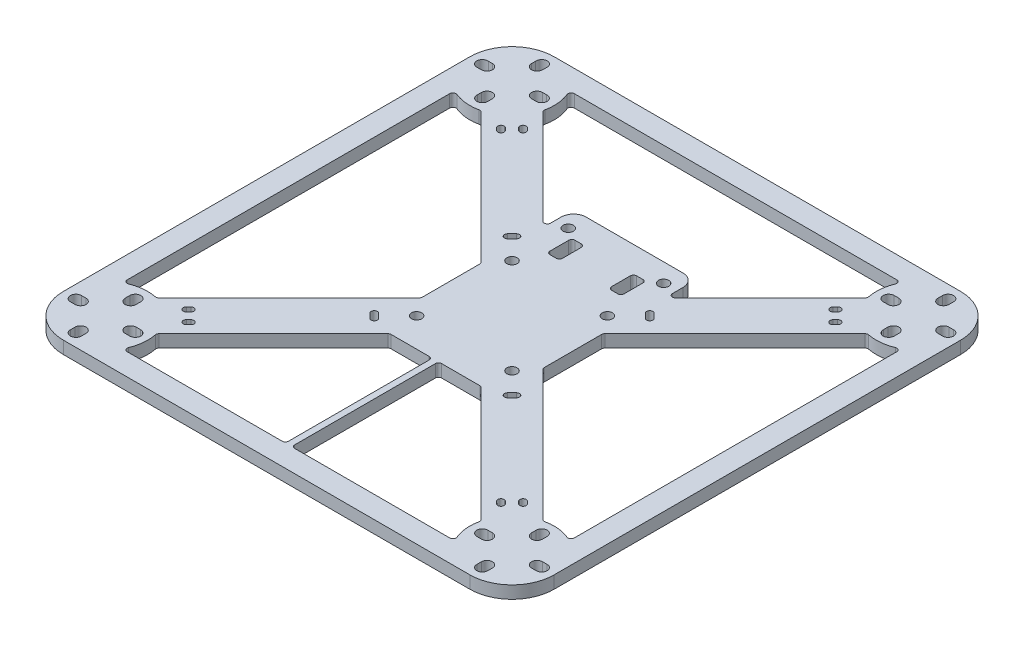
SolidWorks part; units mm, degrees
ref_plane "Front Plane" through (0, 0, 0) normal (0, 0, 1) x (1, 0, 0)
ref_plane "Top Plane" through (0, 0, 0) normal (0, 1, 0) x (1, 0, 0)
ref_plane "Right Plane" through (0, 0, 0) normal (1, 0, 0) x (0, 0, -1)
sketch "Sketch1" plane through (0, 0, 0) normal (0, 1, 0) x (1, 0, 0)
  line L0 (0, 78.5) -> (0, -78.5) construction
  line L1 (-78.5, 78.5) -> (78.5, 78.5)
  line L2 (-78.5, 78.5) -> (-78.5, -78.5)
  line L3 (-78.5, -78.5) -> (78.5, -78.5)
  line L4 (78.5, 78.5) -> (78.5, -78.5)
  line L5 (-78.5, 78.5) -> (78.5, -78.5) construction
  line L6 (-78.5, -78.5) -> (78.5, 78.5) construction
  line L7 (78.5, 0) -> (-78.5, 0) construction
  line L8 (-1, 65) -> (-1, 0) construction
  line L9 (-83.4497, 73.5503) -> (73.5503, -83.4497)
  line L10 (-73.5503, 83.4497) -> (83.4497, -73.5503)
  line L11 (-73.5503, -83.4497) -> (83.4497, 73.5503)
  line L12 (-83.4497, -73.5503) -> (73.5503, 83.4497)
  line L13 (-53.1678, 71.5) -> (53.1678, 71.5)
  line L14 (-53.1678, -71.5) -> (53.1678, -71.5)
  line L15 (71.5, -53.1678) -> (71.5, 53.1678)
  line L16 (-71.5, -53.1678) -> (-71.5, 53.1678)
  circle A0 centre (-65, 65) radius 13.5
  circle A1 centre (-65, 65) radius 64
  circle A2 centre (65, 65) radius 13.5
  circle A3 centre (-65, -65) radius 13.5
  circle A4 centre (65, -65) radius 13.5
  point P0 (0, 0)
  dimension "D1" = 27
  dimension "D2" = 128
  dimension "D3" = 2
  dimension "D4" = 14
  dimension "D5" = 7
extrude "Base shape" add sketch "Sketch1" along normal blind 4 contours L12 A3 L11 L9 | A4 L10 L11 L9 | L11 A2 L12 L10 | L9 A1 L10 A0 | A1 L9 L12 L10 | L12 L9 L11 L10 | L13 A1 L1 A0 | L13 A2 L1 A1 | A4 L4 A2 L15 | A4 L14 A3 L3 | L2 A3 L16 A1 | L2 A1 L16 A0 | A0 | A2 | A4 | A3 region at (-29.268, 0, -75.0845) region at (-75.0845, 0, -29.268) region at (27.4447, 0, -75.1014) region at (-37.8705, 0, -37.8705) region at (-75.1014, 0, 27.4447) region at (-12.3929, 0, -12.3929) region at (30.427, 0, -30.427) region at (0, 0, 0) region at (-30.427, 0, 30.427) region at (30.427, 0, 30.427) region at (75.0932, 0, 0) region at (0, 0, 75.0932)
sketch "Sketch2" plane through (0, 4, 0) normal (0, 1, 0) x (1, 0, 0)
  line L0 (-65, 74.5) -> (-65, 55.5) construction
  line L1 (-74.5, 65) -> (-55.5, 65) construction
  line L2 (0, 78.5) -> (0, -78.5) construction
  line L3 (-65, 78.5) -> (65, 78.5) construction
  line L4 (-65, -78.5) -> (65, -78.5) construction
  line L5 (-78.5, 0) -> (78.5, 0) construction
  line L6 (-78.5, 65) -> (-78.5, -65) construction
  line L7 (78.5, 65) -> (78.5, -65) construction
  line L8 (-66.75, 74.5) -> (-66.75, 73)
  line L9 (-63.25, 74.5) -> (-63.25, 73)
  line L10 (-74.5, 66.75) -> (-73, 66.75)
  line L11 (-74.5, 63.25) -> (-73, 63.25)
  line L12 (-66.75, 57) -> (-66.75, 55.5)
  line L13 (-63.25, 57) -> (-63.25, 55.5)
  line L14 (-57, 66.75) -> (-55.5, 66.75)
  line L15 (-57, 63.25) -> (-55.5, 63.25)
  line L16 (63.25, 57) -> (63.25, 55.5)
  line L17 (66.75, 57) -> (66.75, 55.5)
  line L18 (74.5, 63.25) -> (73, 63.25)
  line L19 (74.5, 66.75) -> (73, 66.75)
  line L20 (63.25, 74.5) -> (63.25, 73)
  line L21 (66.75, 74.5) -> (66.75, 73)
  line L22 (57, 66.75) -> (55.5, 66.75)
  line L23 (57, 63.25) -> (55.5, 63.25)
  line L24 (-66.75, -57) -> (-66.75, -55.5)
  line L25 (-63.25, -57) -> (-63.25, -55.5)
  line L26 (-57, -63.25) -> (-55.5, -63.25)
  line L27 (-57, -66.75) -> (-55.5, -66.75)
  line L28 (-74.5, -63.25) -> (-73, -63.25)
  line L29 (-74.5, -66.75) -> (-73, -66.75)
  line L30 (-63.25, -74.5) -> (-63.25, -73)
  line L31 (-66.75, -74.5) -> (-66.75, -73)
  line L32 (57, -63.25) -> (55.5, -63.25)
  line L33 (57, -66.75) -> (55.5, -66.75)
  line L34 (66.75, -74.5) -> (66.75, -73)
  line L35 (63.25, -74.5) -> (63.25, -73)
  line L36 (74.5, -66.75) -> (73, -66.75)
  line L37 (74.5, -63.25) -> (73, -63.25)
  line L38 (66.75, -57) -> (66.75, -55.5)
  line L39 (63.25, -57) -> (63.25, -55.5)
  circle A0 centre (-65, 65) radius 9.5
  circle A1 centre (-65, 65) radius 8
  circle A2 centre (-65, 74.5) radius 1.75
  circle A3 centre (-65, 55.5) radius 1.75
  circle A4 centre (-57, 65) radius 1.75
  circle A5 centre (-73, 65) radius 1.75
  circle A6 centre (-65, 73) radius 1.75
  circle A7 centre (-55.5, 65) radius 1.75
  circle A8 centre (-74.5, 65) radius 1.75
  circle A9 centre (-65, 57) radius 1.75
  circle A10 centre (65, 57) radius 1.75
  circle A11 centre (65, 55.5) radius 1.75
  circle A12 centre (73, 65) radius 1.75
  circle A13 centre (74.5, 65) radius 1.75
  circle A14 centre (65, 73) radius 1.75
  circle A15 centre (65, 74.5) radius 1.75
  circle A16 centre (57, 65) radius 1.75
  circle A17 centre (55.5, 65) radius 1.75
  circle A18 centre (-65, -57) radius 1.75
  circle A19 centre (-65, -55.5) radius 1.75
  circle A20 centre (-57, -65) radius 1.75
  circle A21 centre (-55.5, -65) radius 1.75
  circle A22 centre (-74.5, -65) radius 1.75
  circle A23 centre (-73, -65) radius 1.75
  circle A24 centre (-65, -74.5) radius 1.75
  circle A25 centre (-65, -73) radius 1.75
  circle A26 centre (55.5, -65) radius 1.75
  circle A27 centre (57, -65) radius 1.75
  circle A28 centre (65, -74.5) radius 1.75
  circle A29 centre (65, -73) radius 1.75
  circle A30 centre (74.5, -65) radius 1.75
  circle A31 centre (73, -65) radius 1.75
  circle A32 centre (65, -55.5) radius 1.75
  circle A33 centre (65, -57) radius 1.75
  dimension "D1" = 19
  dimension "D2" = 16
  dimension "D3" = 3.5
extrude "Motor mounting holes" cut sketch "Sketch2" against normal up to next contours A27 A26 | A26 A27 | A27 A26 | A27 L32 A26 | A27 A26 L33 | A29 A28 | A28 A29 | A28 A29 | A29 L35 A28 | A29 A28 L34 | A31 A30 | A30 A31 | A31 A30 | A31 A30 L37 | A31 L36 A30 | A33 A32 | A32 A33 | A33 A32 | A33 A32 L39 | A33 L38 A32 | A17 A16 | A17 A16 | A16 A17 | L22 A17 A16 | A16 A17 L23 | A11 A10 | A11 A10 | A10 A11 | L16 A11 A10 | A10 A11 L17 | A12 A13 | A13 A12 | A13 A12 | A12 A13 L19 | L18 A13 A12 | A14 A15 | A15 A14 | A15 A14 | A14 A15 L20 | L21 A15 A14 | A8 A5 L10 A0 | A8 A0 L11 A5 | A6 A2 A0 L8 | A6 L9 A0 A2 | A7 A4 L15 A0 | A7 A0 L14 A4 | A9 L12 A0 A3 | A9 A3 A0 L13 | A19 A18 | A19 A18 | A18 A19 | A18 A19 L24 | L25 A19 A18 | A22 A23 | A23 A22 | A23 A22 | A22 A23 L28 | L29 A23 A22 | A21 A20 | A21 A20 | A20 A21 | A20 A21 L26 | L27 A21 A20 | A24 A25 | A25 A24 | A25 A24 | A24 A25 L31 | L30 A25 A24 | A8 | A5 | A2 | A6 | A4 | A7 | A9 | A3 region at (-66.6996, 4, -73.7469) region at (-73.7469, 4, -66.6996) region at (-63.3004, 4, -73.7469) region at (-56.2531, 4, -66.6996) region at (-73.7469, 4, -63.3004) region at (-66.6996, 4, -56.2531) region at (-56.2531, 4, -63.3004) region at (-63.3004, 4, -56.2531) region at (63.3002, 4, -56.25) region at (65, 4, -57.6692) region at (65, 4, -54.8308) region at (66.6998, 4, -56.25) region at (65, 4, -56.25) region at (75.1692, 4, -65) region at (73.75, 4, -63.3002) region at (72.3308, 4, -65) region at (73.75, 4, -65) region at (73.75, 4, -66.6998) region at (63.3002, 4, -73.75) region at (65, 4, -75.1692) region at (65, 4, -72.3308) region at (66.6998, 4, -73.75) region at (65, 4, -73.75) region at (56.25, 4, -66.6998) region at (57.6692, 4, -65) region at (54.8308, 4, -65) region at (56.25, 4, -65) region at (56.25, 4, -63.3002) region at (-65, 4, 57.6692) region at (-66.6998, 4, 56.25) region at (-65, 4, 54.8308) region at (-63.3002, 4, 56.25) region at (-65, 4, 56.25) region at (-57.6692, 4, 65) region at (-56.25, 4, 63.3002) region at (-54.8308, 4, 65) region at (-56.25, 4, 66.6998) region at (-56.25, 4, 65) region at (-75.1692, 4, 65) region at (-73.75, 4, 63.3002) region at (-72.3308, 4, 65) region at (-73.75, 4, 66.6998) region at (-73.75, 4, 65) region at (-63.3002, 4, 73.75) region at (-65, 4, 75.1692) region at (-65, 4, 72.3308) region at (-66.6998, 4, 73.75) region at (-65, 4, 73.75) region at (56.25, 4, 63.3002) region at (57.6692, 4, 65) region at (54.8308, 4, 65) region at (56.25, 4, 65) region at (56.25, 4, 66.6998) region at (66.6998, 4, 73.75) region at (65, 4, 75.1692) region at (65, 4, 72.3308) region at (63.3002, 4, 73.75) region at (65, 4, 73.75) region at (75.1692, 4, 65) region at (73.75, 4, 66.6998)
sketch "Sketch5" plane through (0, 0, 0) normal (0, -1, 0) x (1, 0, 0)
  line L3 (-19.5, 10.25) -> (19.5, 10.25)
  line L4 (-19.5, 10.25) -> (-19.5, -10.25)
  line L7 (-19.5, -10.25) -> (19.5, -10.25)
  line L8 (19.5, 10.25) -> (19.5, -10.25)
  line L16 (-15.5, -39.2) -> (15.5, -39.2)
  line L17 (19.5, -35.2) -> (19.5, -10.25)
  line L18 (19.5, -10.25) -> (17.5, -10.25)
  line L19 (17.5, -10.25) -> (17.5, 10.25)
  line L20 (17.5, 10.25) -> (19.5, 10.25)
  line L21 (19.5, 10.25) -> (19.5, 24.5)
  line L22 (19.5, 24.5) -> (-19.5, 24.5)
  line L23 (-19.5, 24.5) -> (-19.5, 10.25)
  line L24 (-19.5, 10.25) -> (-17.5, 10.25)
  line L25 (-17.5, 10.25) -> (-17.5, -10.25)
  line L26 (-17.5, -10.25) -> (-19.5, -10.25)
  line L27 (-19.5, -10.25) -> (-19.5, -35.2)
  line L28 (-15.5, -39.2) -> (15.5, -39.2)
  line L29 (19.5, -35.2) -> (19.5, -10.25)
  line L30 (19.5, -10.25) -> (17.5, -10.25)
  line L31 (17.5, -10.25) -> (17.5, 10.25)
  line L32 (17.5, 10.25) -> (19.5, 10.25)
  line L33 (19.5, 10.25) -> (19.5, 24.5)
  line L34 (19.5, 24.5) -> (-19.5, 24.5)
  line L35 (-19.5, 24.5) -> (-19.5, 10.25)
  line L36 (-19.5, 10.25) -> (-17.5, 10.25)
  line L37 (-17.5, 10.25) -> (-17.5, -10.25)
  line L38 (-17.5, -10.25) -> (-19.5, -10.25)
  line L39 (-19.5, -10.25) -> (-19.5, -35.2)
  arc A2 (15.5, -39.2) -> (19.5, -35.2) centre (15.5, -35.2) ccw
  arc A3 (-19.5, -35.2) -> (-15.5, -39.2) centre (-15.5, -35.2) ccw
  arc A4 (15.5, -39.2) -> (19.5, -35.2) centre (15.5, -35.2) ccw
  arc A5 (-19.5, -35.2) -> (-15.5, -39.2) centre (-15.5, -35.2) ccw
  dimension "D1" = 0
extrude "OSD cover" add sketch "Sketch5" against normal up to surface (4 mm away) contours L34 L35 L3 L33 | L3 L37 L7 L31 | L37 L3 L4 L7 | L31 L7 L8 L3 | L39 A5 L28 A4 L29 L7 region at (0, 0, 17.375) region at (-18.5, 0, 0) region at (0, 0, 0) region at (0, 0, -24.6419) region at (18.5, 0, 0) up to face at (65, 4, 73.75)
sketch "Sketch7" plane through (0, 4, 0) normal (0, 1, 0) x (1, 0, 0)
  line L0 (18, 23) -> (-18, 23) construction
  line L1 (-8.85, 23) -> (-10.85, 23)
  line L2 (-7.85, 24) -> (-7.85, 30)
  line L3 (-8.85, 31) -> (-10.85, 31)
  line L4 (-11.85, 24) -> (-11.85, 30)
  line L5 (-7.85, 39.2) -> (-7.85, 23) construction
  line L6 (0, -24.5) -> (0, 39.2) construction
  line L10 (7.85, 39.2) -> (-4.95, 39.2) construction
  line L11 (8.85, 31) -> (10.85, 31)
  line L12 (11.85, 24) -> (11.85, 30)
  line L13 (8.85, 23) -> (10.85, 23)
  line L14 (7.85, 24) -> (7.85, 30)
  line L15 (14.6005, -24.5) -> (-14.6005, -24.5) construction
  circle A0 centre (-15.25, -15.25) radius 1.65 construction
  circle A1 centre (-15.25, 15.25) radius 1.65 construction
  circle A2 centre (-15.25, 33.25) radius 1.65 construction
  circle A3 centre (15.25, 33.25) radius 1.65 construction
  circle A4 centre (15.25, 15.25) radius 1.65 construction
  circle A5 centre (15.25, -15.25) radius 1.65 construction
  circle A6 centre (-15.25, -15.25) radius 1.65
  circle A7 centre (-15.25, 15.25) radius 1.65
  circle A8 centre (-15.25, 33.25) radius 1.65
  circle A9 centre (15.25, 33.25) radius 1.65
  circle A10 centre (15.25, 15.25) radius 1.65
  circle A11 centre (15.25, -15.25) radius 1.65
  arc A12 (8.85, 23) -> (7.85, 24) centre (8.85, 24) cw
  arc A13 (11.85, 24) -> (10.85, 23) centre (10.85, 24) cw
  arc A14 (10.85, 31) -> (11.85, 30) centre (10.85, 30) cw
  arc A15 (8.85, 31) -> (7.85, 30) centre (8.85, 30) ccw
  arc A16 (-10.85, 23) -> (-11.85, 24) centre (-10.85, 24) cw
  arc A17 (-8.85, 23) -> (-7.85, 24) centre (-8.85, 24) ccw
  arc A18 (-7.85, 30) -> (-8.85, 31) centre (-8.85, 30) ccw
  arc A19 (-10.85, 31) -> (-11.85, 30) centre (-10.85, 30) ccw
  point P29 (0, 0)
  point P40 (7.85, 23)
  point P43 (11.85, 23)
  point P46 (11.85, 31)
  point P49 (7.85, 31)
  point P52 (-11.85, 23)
  point P55 (-7.85, 23)
  point P58 (-7.85, 31)
  point P61 (-11.85, 31)
  dimension "D2" = 8
  dimension "D3" = 1
  dimension "D1" = 4
extrude "Main holes" cut sketch "Sketch7" against normal up to next contours A11 | A10 | A9 | A8 | A7 | A6 | L3 A19 L4 A16 L1 A17 L2 A18 | L11 A14 L12 A13 L13 A12 L14 A15
sketch "Sketch8" plane through (0, 0, 0) normal (0, -1, 0) x (1, 0, 0)
  line L0 (0, 78.5) -> (0, -71.5) construction
  line L1 (-65, 78.5) -> (65, 78.5) construction
  line L2 (-53.1678, -71.5) -> (53.1678, -71.5) construction
  line L4 (-1, 24.5) -> (1, 24.5)
  line L5 (-1, 24.5) -> (-1, 71.5)
  line L6 (-1, 71.5) -> (1, 71.5)
  line L7 (1, 24.5) -> (1, 71.5)
  line L8 (-53.1678, 71.5) -> (53.1678, 71.5) construction
  line L9 (0, 71.5) -> (0, 24.5) construction
  line L10 (-19.5, 24.5) -> (19.5, 24.5) construction
  point P10 (-1, 25.576)
  point P16 (0, 0)
  dimension "D1" = 2
extrude "VTX wire support" add sketch "Sketch8" against normal up to surface (4 mm away) up to face at (9.85, 4, -27)
sketch "Sketch9" plane through (0, 0, 0) normal (0, -1, 0) x (1, 0, 0)
  line L0 (22.0251, 22.0251) -> (74.5459, 74.5459) construction
  line L1 (46.7739, 56.6734) -> (56.6734, 46.7739) construction
  line L2 (19.9038, 22.7322) -> (22.7322, 19.9038)
  line L3 (19.9038, 22.7322) -> (21.318, 24.1464)
  line L4 (22.7322, 19.9038) -> (24.1464, 21.318)
  line L5 (21.318, 24.1464) -> (24.1464, 21.318)
  line L6 (26.9749, 17.0754) -> (17.0754, 26.9749) construction
  line L7 (19.5, 9.6005) -> (61.7873, 51.8878) construction
  line L8 (53.1378, 48.1881) -> (55.2591, 50.3094)
  line L9 (14.6005, 24.5) -> (51.8878, 61.7873) construction
  line L10 (19.9038, 22.7322) -> (24.1464, 21.318) construction
  line L11 (0, 78.5) -> (0, -78.5) construction
  line L12 (-65, 78.5) -> (65, 78.5) construction
  line L13 (-65, -78.5) -> (65, -78.5) construction
  line L14 (-78.5, 0) -> (78.5, 0) construction
  line L15 (-78.5, -65) -> (-78.5, 65) construction
  line L16 (78.5, -65) -> (78.5, 65) construction
  line L17 (22.7322, 19.9038) -> (21.318, 24.1464) construction
  line L18 (-19.9038, 22.7322) -> (-21.318, 24.1464)
  line L19 (-19.9038, 22.7322) -> (-22.7322, 19.9038)
  line L20 (-22.7322, 19.9038) -> (-24.1464, 21.318)
  line L21 (-21.318, 24.1464) -> (-24.1464, 21.318)
  line L22 (19.9038, -22.7322) -> (21.318, -24.1464)
  line L23 (19.9038, -22.7322) -> (22.7322, -19.9038)
  line L24 (22.7322, -19.9038) -> (24.1464, -21.318)
  line L25 (21.318, -24.1464) -> (24.1464, -21.318)
  line L26 (-21.318, -24.1464) -> (-24.1464, -21.318)
  line L27 (-22.7322, -19.9038) -> (-24.1464, -21.318)
  line L28 (-19.9038, -22.7322) -> (-22.7322, -19.9038)
  line L29 (-19.9038, -22.7322) -> (-21.318, -24.1464)
  line L30 (53.1378, 48.1881) -> (51.7236, 49.6023)
  line L31 (55.2591, 50.3094) -> (53.8449, 51.7236)
  line L32 (51.7236, 49.6023) -> (53.8449, 51.7236)
  line L33 (53.1378, 48.1881) -> (53.8449, 51.7236) construction
  line L34 (55.2591, 50.3094) -> (51.7236, 49.6023) construction
  line L35 (52.4307, 48.8952) -> (54.552, 51.0165) construction
  line L36 (48.1881, 53.1378) -> (49.6023, 51.7236)
  line L37 (49.6023, 51.7236) -> (51.7236, 53.8449)
  line L38 (50.3094, 55.2591) -> (51.7236, 53.8449)
  line L39 (48.1881, 53.1378) -> (50.3094, 55.2591)
  line L40 (-53.1378, 48.1881) -> (-55.2591, 50.3094)
  line L41 (-55.2591, 50.3094) -> (-53.8449, 51.7236)
  line L42 (-51.7236, 49.6023) -> (-53.8449, 51.7236)
  line L43 (-53.1378, 48.1881) -> (-51.7236, 49.6023)
  line L44 (-48.1881, 53.1378) -> (-50.3094, 55.2591)
  line L45 (-50.3094, 55.2591) -> (-51.7236, 53.8449)
  line L46 (-49.6023, 51.7236) -> (-51.7236, 53.8449)
  line L47 (-48.1881, 53.1378) -> (-49.6023, 51.7236)
  line L48 (53.1378, -48.1881) -> (55.2591, -50.3094)
  line L49 (53.1378, -48.1881) -> (51.7236, -49.6023)
  line L50 (51.7236, -49.6023) -> (53.8449, -51.7236)
  line L51 (55.2591, -50.3094) -> (53.8449, -51.7236)
  line L52 (48.1881, -53.1378) -> (49.6023, -51.7236)
  line L53 (48.1881, -53.1378) -> (50.3094, -55.2591)
  line L54 (50.3094, -55.2591) -> (51.7236, -53.8449)
  line L55 (49.6023, -51.7236) -> (51.7236, -53.8449)
  line L56 (-48.1881, -53.1378) -> (-49.6023, -51.7236)
  line L57 (-49.6023, -51.7236) -> (-51.7236, -53.8449)
  line L58 (-50.3094, -55.2591) -> (-51.7236, -53.8449)
  line L59 (-48.1881, -53.1378) -> (-50.3094, -55.2591)
  line L60 (-53.1378, -48.1881) -> (-51.7236, -49.6023)
  line L61 (-51.7236, -49.6023) -> (-53.8449, -51.7236)
  line L62 (-55.2591, -50.3094) -> (-53.8449, -51.7236)
  line L63 (-53.1378, -48.1881) -> (-55.2591, -50.3094)
  arc A0 (78.5, 65) -> (65, 78.5) centre (65, 65) ccw construction
  circle A1 centre (21.318, 22.7322) radius 1
  circle A2 centre (22.7322, 21.318) radius 1
  circle A3 centre (-22.7322, 21.318) radius 1
  circle A4 centre (-21.318, 22.7322) radius 1
  circle A5 centre (21.318, -22.7322) radius 1
  circle A6 centre (22.7322, -21.318) radius 1
  circle A7 centre (-21.318, -22.7322) radius 1
  circle A8 centre (-22.7322, -21.318) radius 1
  circle A9 centre (53.1378, 49.6023) radius 1
  circle A10 centre (53.8449, 50.3094) radius 1
  circle A11 centre (50.3094, 53.8449) radius 1
  circle A12 centre (49.6023, 53.1378) radius 1
  circle A13 centre (-50.3094, 53.8449) radius 1
  circle A14 centre (-49.6023, 53.1378) radius 1
  circle A15 centre (-53.1378, 49.6023) radius 1
  circle A16 centre (-53.8449, 50.3094) radius 1
  circle A17 centre (53.1378, -49.6023) radius 1
  circle A18 centre (53.8449, -50.3094) radius 1
  circle A19 centre (49.6023, -53.1378) radius 1
  circle A20 centre (50.3094, -53.8449) radius 1
  circle A21 centre (-53.8449, -50.3094) radius 1
  circle A22 centre (-53.1378, -49.6023) radius 1
  circle A23 centre (-49.6023, -53.1378) radius 1
  circle A24 centre (-50.3094, -53.8449) radius 1
  point P59 (53.4914, 49.9558)
  dimension "D3" = 42
  dimension "D4" = 3.5
  dimension "D1" = 2
  dimension "D2" = 4
  dimension "D5" = 3
  dimension "D6" = 2
  dimension "D7" = 3
extrude "ESC cuts" cut sketch "Sketch9" against normal up to next contours A2 | A1 | A2 L5 A1 | A2 A1 L2 | A3 | A4 | L19 A4 A3 | A3 A4 L21 | A8 L26 A7 | A8 | A8 A7 L28 | A7 | A5 | A6 | L25 A6 A5 | A5 A6 L23 | A10 A9 | A9 A10 | A9 A10 | A10 L32 A9 | A10 A9 L8 | A12 A11 | A12 A11 | A11 A12 | L39 A12 A11 | A11 A12 L37 | A14 A13 | A13 A14 | A14 A13 | A14 A13 L46 | A14 L44 A13 | A15 A16 | A16 A15 | A16 A15 | L42 A16 A15 | A15 A16 L40 | A22 A21 | A21 A22 | A21 A22 | A22 L63 A21 | A22 A21 L61 | A23 A24 | A24 A23 | A24 A23 | L57 A24 A23 | A23 A24 L59 | A20 A19 | A19 A20 | A20 A19 | A20 L55 A19 | A20 A19 L53 | A17 A18 | A18 A17 | A18 A17 | A17 A18 L48 | L50 A18 A17 region at (21.476, 0, 21.476) region at (21.318, 0, 22.7322) region at (22.7322, 0, 21.318) region at (22.5743, 0, 22.5743) region at (54.1704, 0, 49.2768) region at (52.9108, 0, 49.3753) region at (54.0719, 0, 50.5364) region at (53.4914, 0, 49.9558) region at (52.8123, 0, 50.6349) region at (-21.318, 0, 22.7322) region at (-21.476, 0, 21.476) region at (-22.5743, 0, 22.5743) region at (-22.7322, 0, 21.318) region at (21.318, 0, -22.7322) region at (21.476, 0, -21.476) region at (22.5743, 0, -22.5743) region at (22.7322, 0, -21.318) region at (-22.5743, 0, -22.5743) region at (-21.318, 0, -22.7322) region at (-22.7322, 0, -21.318) region at (-21.476, 0, -21.476) region at (49.3753, 0, 52.9108) region at (49.2768, 0, 54.1704) region at (50.6349, 0, 52.8123) region at (50.5364, 0, 54.0719) region at (49.9558, 0, 53.4914) region at (-54.1704, 0, 49.2768) region at (-52.9108, 0, 49.3753) region at (-54.0719, 0, 50.5364) region at (-53.4914, 0, 49.9558) region at (-52.8123, 0, 50.6349) region at (-49.2768, 0, 54.1704) region at (-49.3753, 0, 52.9108) region at (-50.5364, 0, 54.0719) region at (-49.9558, 0, 53.4914) region at (-50.6349, 0, 52.8123) region at (54.1704, 0, -49.2768) region at (52.9108, 0, -49.3753) region at (54.0719, 0, -50.5364) region at (53.4914, 0, -49.9558) region at (52.8123, 0, -50.6349) region at (49.3753, 0, -52.9108) region at (49.2768, 0, -54.1704) region at (50.6349, 0, -52.8123) region at (50.5364, 0, -54.0719) region at (49.9558, 0, -53.4914) region at (-49.3753, 0, -52.9108) region at (-49.2768, 0, -54.1704) region at (-50.6349, 0, -52.8123) region at (-50.5364, 0, -54.0719) region at (-49.9558, 0, -53.4914) region at (-52.9108, 0, -49.3753) region at (-54.1704, 0, -49.2768) region at (-54.0719, 0, -50.5364) region at (-53.4914, 0, -49.9558) region at (-52.8123, 0, -50.6349)
fillet "Milling fillets" radius 1 28 edges at (53.1678, 2, -71.5) (51.8878, 2, -61.7873) (-53.1678, 2, -71.5) (-51.8878, 2, -61.7873) (-61.7873, 2, -51.8878) (-71.5, 2, -53.1678) (-71.5, 2, 53.1678) (-61.7873, 2, 51.8878) (-51.8878, 2, 61.7873) (-53.1678, 2, 71.5) (-1, 2, 71.5) (1, 2, 71.5) (51.8878, 2, 61.7873) (53.1678, 2, 71.5) (61.7873, 2, -51.8878) (71.5, 2, -53.1678) (61.7873, 2, 51.8878) (71.5, 2, 53.1678) (19.5, 2, -29.3995) (-19.5, 2, -29.3995) (-19.5, 2, 9.6005) (-19.5, 2, -9.6005) (19.5, 2, -9.6005) (19.5, 2, 9.6005) (1, 2, 24.5) (-14.6005, 2, 24.5) (-1, 2, 24.5) (14.6005, 2, 24.5)
sketch "Sketch3" plane through (0, 0, 0) normal (0, -1, 0) x (1, 0, 0)
  line L0 (0, -71.5) -> (0, -83.5) construction
  line L1 (-51.5836, -71.5) -> (51.5836, -71.5) construction
  line L2 (-65, -78.5) -> (65, -78.5) construction
  line L3 (0, -83.5) -> (-5, -78.5)
  line L4 (-5, -78.5) -> (5, -78.5)
  line L5 (0, -83.5) -> (5, -78.5)
  point P10 (0, -78.5)
  dimension "D1" = 5
  dimension "D2" = 45
extrude "TEST Forward arrow" [suppressed] add sketch "Sketch3" against normal up to surface (4 mm away) contours L4 L0 L5 | L0 L4 L3 up to face at (-49.9558, 4, 53.4914)
sketch "Sketch10" plane through (0, 4, 0) normal (0, 1, 0) x (1, 0, 0)
  line L0 (-65, -78.5) -> (65, -78.5) construction
  line L1 (29.5, 78.5) -> (78.5, 78.5)
  line L2 (29.5, 78.5) -> (29.5, -78.5)
  line L3 (29.5, -78.5) -> (78.5, -78.5)
  line L4 (78.5, 78.5) -> (78.5, -78.5)
  line L5 (78.5, 65) -> (78.5, -65) construction
  line L6 (19.5, 9.1863) -> (19.5, -9.1863) construction
  line L8 (-65, 78.5) -> (65, 78.5) construction
  dimension "D1" = 10
extrude "TEST print cut" [suppressed] cut sketch "Sketch10" against normal up to next
equation "\"MotorDiameter\"=27"
equation "\"D1@Sketch1\"=\"MotorDiameter\""
equation "\"PropDiameter\"=128"
equation "\"D2@Sketch1\"=\"PropDiameter\""
equation "\"PropDistance\"=2"
equation "\"D3@Sketch1\"=\"PropDistance\""
equation "\"ArmWidth\"=14"
equation "\"D4@Sketch1\"=\"ArmWidth\""
equation "\"FrameDepth\"=4"
equation "\"D1@Base shape\" = \"FrameDepth\""
equation "\"D5@Sketch1\"=\"ArmWidth\"/2"
equation "\"MotorHoleOuterDiameter\"=19"
equation "\"D1@Sketch2\"=\"MotorHoleOuterDiameter\""
equation "\"MotorHoleInnerDiameter\"=16"
equation "\"D2@Sketch2\"=\"MotorHoleInnerDiameter\""
equation "\"MotorHoleDiameter\"=3.5"
equation "\"D3@Sketch2\"=\"MotorHoleDiameter\""
